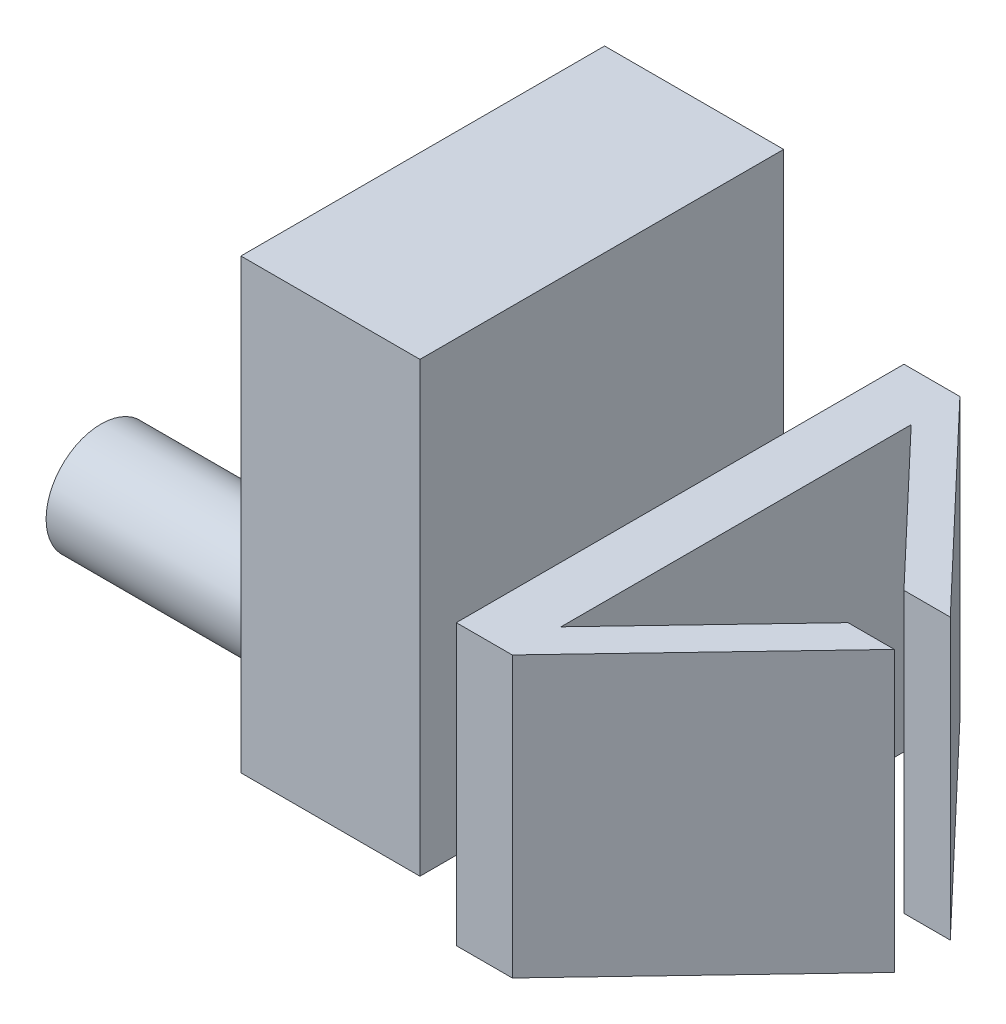
SolidWorks part; units mm, degrees
material "ABS PC"
ref_plane "Front Plane" through (0, 0, 0) normal (0, 0, 1) x (1, 0, 0)
ref_plane "Top Plane" through (0, 0, 0) normal (0, 1, 0) x (1, 0, 0)
ref_plane "Right Plane" through (0, 0, 0) normal (1, 0, 0) x (0, 0, -1)
sketch "Sketch1" plane through (0, 0, 0) normal (0, 1, 0) x (1, 0, 0)
  line L0 (0, 0) -> (4.064, 0) construction
  line L1 (4.064, -8.255) -> (-4.064, -8.255)
  line L2 (4.064, -8.255) -> (4.064, 8.255)
  line L3 (4.064, 8.255) -> (-4.064, 8.255)
  line L4 (-4.064, -8.255) -> (-4.064, 8.255)
  line L5 (4.064, -8.255) -> (-4.064, 8.255) construction
  line L6 (4.064, 8.255) -> (-4.064, -8.255) construction
  point P0 (0, 0)
  dimension "D1" = 8.128
  dimension "D2" = 16.51
extrude "Boss-Extrude1" add sketch "Sketch1" along normal blind 20.32
sketch "Sketch2" plane through (-4.064, 0, 0) normal (-1, 0, 0) x (0, 0, 1)
  line L0 (8.255, 20.32) -> (8.255, 0) construction
  circle A0 centre (4.445, 4.2371) radius 2.4932
  dimension "D1" = 3.81
extrude "Boss-Extrude2" add sketch "Sketch2" along normal blind 10.16
fillet "Fillet2" radius 1.27 1 edges at (-4.064, 4.2371, 1.9518)
sketch "Sketch3" plane through (4.064, 0, 0) normal (1, 0, 0) x (0, 0, -1)
  line L0 (-8.255, 0) -> (8.255, 0) construction
  line L1 (-4.445, 3.81) -> (4.445, 3.81)
  line L2 (-4.445, 3.81) -> (-4.445, 0)
  line L3 (-4.445, 0) -> (4.445, 0)
  line L4 (4.445, 3.81) -> (4.445, 0)
  line L6 (-4.445, 3.81) -> (0, 0) construction
  line L7 (0, 0) -> (4.445, 3.81) construction
  dimension "D1" = 8.89
  dimension "D2" = 3.81
extrude "Boss-Extrude3" add sketch "Sketch3" along normal blind 3.556
fillet "Fillet3" radius 1.27 1 edges at (4.064, 3.81, 0)
sketch "Sketch5" plane through (0, 0, 0) normal (0, -1, 0) x (-1, 0, 0)
  line L0 (-7.62, -4.445) -> (-7.62, 4.445) construction
  line L1 (-10.16, -10.16) -> (-7.62, -10.16)
  line L2 (-10.16, -7.9483) -> (-10.16, 7.9483)
  line L3 (-16.51, 1.27) -> (-18.613, 1.27)
  line L4 (-7.62, -10.16) -> (-7.62, 10.16)
  line L5 (0, 0) -> (-7.62, -10.16) construction
  line L6 (-16.51, 1.27) -> (-10.16, 7.9483)
  line L7 (-10.16, -10.16) -> (-18.613, -1.27)
  line L8 (-10.16, 10.16) -> (-18.613, 1.27)
  line L9 (-10.16, 10.16) -> (-7.62, 10.16)
  line L10 (-16.51, -1.27) -> (-10.16, -7.9483)
  line L11 (-16.51, -1.27) -> (-18.613, -1.27)
  line L12 (-7.62, 0) -> (-10.16, 0) construction
  dimension "D1" = 2.54
  dimension "D2" = 10.16
  dimension "D3" = 6.35
  dimension "D4" = 1.27
  dimension "D5" = 1.524
extrude "Boss-Extrude4" add sketch "Sketch5" against normal blind 12.7
fillet "Fillet4" radius 3.81 1 edges at (7.62, 3.81, 0)
